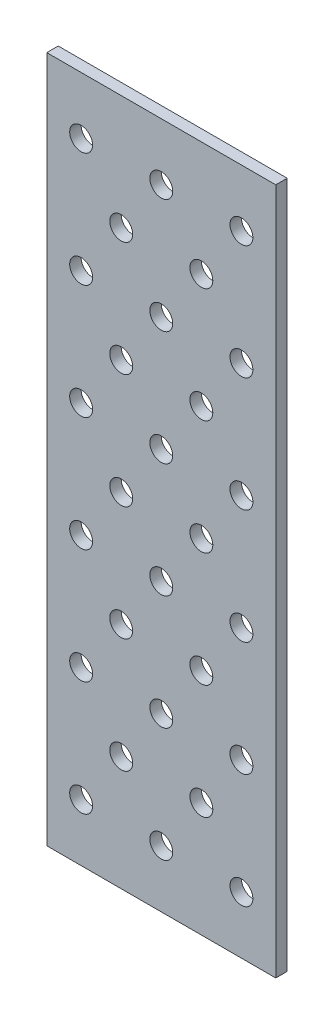
SolidWorks part; units mm, degrees
ref_plane "Front Plane" through (0, 0, 0) normal (0, 0, 1) x (1, 0, 0)
ref_plane "Top Plane" through (0, 0, 0) normal (0, 1, 0) x (1, 0, 0)
ref_plane "Right Plane" through (0, 0, 0) normal (1, 0, 0) x (0, 0, -1)
sketch "Sketch1" plane through (0, 0, 0) normal (0, 0, 1) x (1, 0, 0)
  line L0 (-20, 50) -> (20, 50) construction
  line L1 (-20, 60) -> (20, 60)
  line L2 (-20, 60) -> (-20, -60)
  line L3 (-20, -60) -> (20, -60)
  line L4 (20, 60) -> (20, -60)
  line L5 (-20, 60) -> (20, -60) construction
  line L6 (-20, -60) -> (20, 60) construction
  line L7 (-20, 40) -> (20, 40) construction
  line L8 (0, 60) -> (0, -60) construction
  line L9 (-20, 30) -> (20, 30) construction
  line L10 (-20, 10) -> (20, 10) construction
  line L11 (-20, -10) -> (20, -10) construction
  line L12 (-20, -30) -> (20, -30) construction
  line L13 (-20, -50) -> (20, -50) construction
  circle A0 centre (-14, 50) radius 2
  circle A1 centre (0, 50) radius 2
  circle A2 centre (14, 50) radius 2
  circle A3 centre (-7, 40) radius 2
  circle A4 centre (7, 40) radius 2
  circle A5 centre (-14, 30) radius 2
  circle A6 centre (-7, 20) radius 2
  circle A7 centre (7, 20) radius 2
  circle A8 centre (0, 30) radius 2
  circle A9 centre (14, 30) radius 2
  circle A10 centre (-14, 10) radius 2
  circle A11 centre (-7, 0) radius 2
  circle A12 centre (7, 0) radius 2
  circle A13 centre (0, 10) radius 2
  circle A14 centre (14, 10) radius 2
  circle A15 centre (-14, -10) radius 2
  circle A16 centre (-7, -20) radius 2
  circle A17 centre (7, -20) radius 2
  circle A18 centre (0, -10) radius 2
  circle A19 centre (14, -10) radius 2
  circle A20 centre (-14, -30) radius 2
  circle A21 centre (-7, -40) radius 2
  circle A22 centre (7, -40) radius 2
  circle A23 centre (0, -30) radius 2
  circle A24 centre (14, -30) radius 2
  circle A25 centre (-14, -50) radius 2
  circle A28 centre (0, -50) radius 2
  circle A29 centre (14, -50) radius 2
  arc A30 (-9, -60) -> (-5, -60) centre (-7, -60) ccw
  arc A31 (9, -60) -> (5, -60) centre (7, -60) ccw
  point P0 (0, 0)
  point P23 (0, 40)
  dimension "D5" = 14
  dimension "D6" = 14
  dimension "D7" = 7
  dimension "D8" = 7
  dimension "D9" = 4
  dimension "D1" = 120
  dimension "D2" = 40
  dimension "D3" = 10
  dimension "D4" = 10
  dimension "D11" = 10
  dimension "D10" = 6
base flange "Base-Flange1" sketch "Sketch1" thickness 2 reverse thickness direction no parameters "D1"=0.7366
sketch "Bend-Lines1" [suppressed] plane through (0, 0, 0) normal (0, 1, 0) x (1, 0, 0)
sketch "Bounding-Box1" [suppressed] plane through (0, 0, 0) normal (0, 1, 0) x (1, 0, 0)
sheet metal parameters "Sheet-Metal1" thickness 2 parameters "D1"=0.7366
flat pattern "Flat-Pattern1" [suppressed]
sketch "Bend-Lines2" plane through (0, 0, 0) normal (0, 1, 0) x (1, 0, 0)
sketch3d "Bounding-Box2" [suppressed]
  line L0 (20, 60, 0) -> (20, -60, 0) construction
  line L1 (-20, 60, 0) -> (-20, -60, 0) construction
  line L2 (20, 60, 0) -> (-20, 60, 0) construction
  line L3 (20, -60, 0) -> (-20, -60, 0) construction
